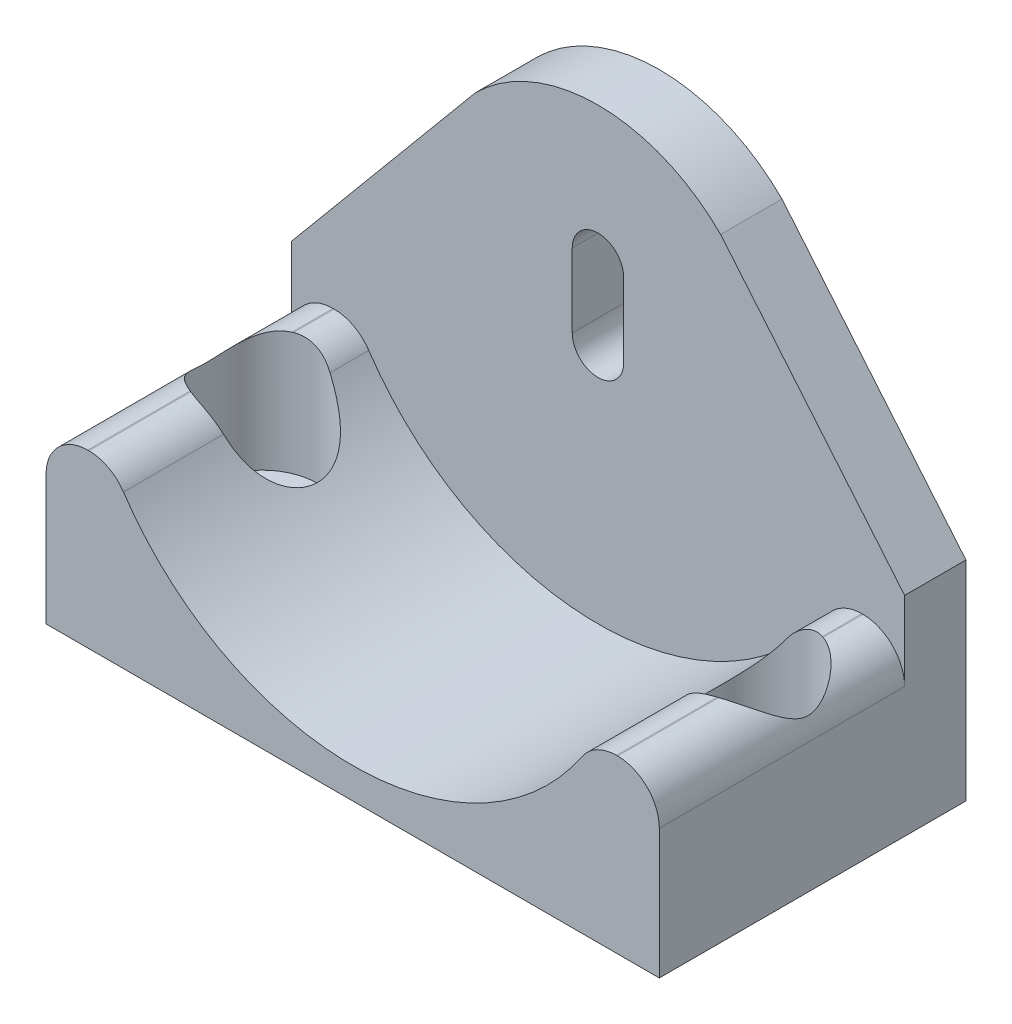
SolidWorks part; units mm, degrees
ref_plane "前视基准面" through (0, 0, 0) normal (0, 0, 1) x (1, 0, 0)
ref_plane "上视基准面" through (0, 0, 0) normal (0, 1, 0) x (1, 0, 0)
ref_plane "右视基准面" through (0, 0, 0) normal (1, 0, 0) x (0, 0, -1)
sketch "草图1" plane through (0, 0, 0) normal (0, 0, 1) x (1, 0, 0)
  line L1 (-28.2986, 3.0382) -> (21.7014, 3.0382)
  line L2 (-28.2986, 3.0382) -> (-28.2986, -13.9757)
  line L3 (-28.2986, -13.9757) -> (21.7014, -13.9757)
  line L4 (21.7014, 3.0382) -> (21.7014, -13.9757)
  line L7 (-13.2986, 21.0243) -> (-28.2986, 3.0382)
  line L8 (6.7014, 21.0243) -> (21.7014, 3.0382)
  line L12 (-3.2986, 14.0243) -> (-3.2986, 8.0243) construction
  line L13 (-1.1986, 14.0243) -> (-1.1986, 8.0243)
  line L14 (-5.3986, 14.0243) -> (-5.3986, 8.0243)
  arc A1 (-13.2986, 21.0243) -> (6.7014, 21.0243) centre (-3.2986, 11.0243) cw
  arc A2 (-1.1986, 14.0243) -> (-5.3986, 14.0243) centre (-3.2986, 14.0243) ccw
  arc A3 (-5.3986, 8.0243) -> (-1.1986, 8.0243) centre (-3.2986, 8.0243) ccw
  arc A5 (-24.3336, 3.0382) -> (17.7364, 3.0382) centre (-3.2986, 11.0243) ccw
  point P19 (-3.2986, 11.0243)
  dimension "D9" = 2.1
  dimension "D1" = 50
extrude "凸台-拉伸1" add sketch "草图1" along normal blind 25 contours A5 L1 L2 L3 L4 region at (-26.3161, 2.51, 0)
extrude "凸台-拉伸2" add sketch "草图1<5>" along normal blind 5 contours L1 A5 | A1 L7 L1 L8 A3 L14 A2 L13 region at (-20.3787, 11.6811, 0) region at (-3.2986, -2.9654, 0)
sketch "草图1<5>" plane through (0, 0, 0) normal (0, 0, 1) x (1, 0, 0) same geometry as "草图1"
sketch "草图3" plane through (0, 0, 25) normal (0, 0, 1) x (1, 0, 0)
  line L0 (-35.9406, 0) -> (33.432, 0)
  line L1 (-28.2986, 0) -> (-28.2986, 3.0382)
  line L2 (-28.2986, 3.0382) -> (-28.2986, -13.9757) construction
  line L3 (-28.2986, 3.0382) -> (-24.3336, 3.0382)
  line L4 (-28.2986, 3.0382) -> (-24.3336, 3.0382) construction
  line L5 (-24.3336, 3.0382) -> (-22.9128, 0)
  line L6 (-22.9128, 0) -> (-28.2986, 0)
  line L7 (16.3155, 0) -> (17.7364, 3.0382)
  line L8 (17.7364, 3.0382) -> (21.7014, 3.0382)
  line L9 (21.7014, 3.0382) -> (21.7014, 0)
  line L10 (21.7014, 3.0382) -> (21.7014, -13.9757) construction
  line L11 (21.7014, 0) -> (16.3155, 0)
  arc A0 (-24.3336, 3.0382) -> (17.7364, 3.0382) centre (-3.2986, 11.0243) ccw construction
  arc M1 (17.7364, 3.0382) -> (-24.3336, 3.0382) centre (-3.2986, 11.0243) cw
  line M2 (-24.3336, 3.0382) -> (-28.2986, 3.0382)
  line M3 (-28.2986, 3.0382) -> (-28.2986, -13.9757)
  line M5 (21.7014, -13.9757) -> (21.7014, 3.0382)
  line M6 (21.7014, 3.0382) -> (17.7364, 3.0382)
extrude "切除-拉伸2" cut sketch "草图3" against normal blind 20 contours L0 M3 M1 M2 | L0 M1 M5 M6 region at (-25.9658, 1.4415, 25) region at (19.3685, 1.4415, 25)
fillet "圆角3" radius 3.4 2 edges at (-22.9128, 0, 15) (-28.2986, 0, 15)
fillet "圆角4" radius 3.4 2 edges at (21.7014, 0, 15) (16.3155, 0, 15)
sketch "草图5" plane through (0, -13.9757, 0) normal (0, -1, 0) x (-1, 0, 0)
  circle A0 centre (23.1599, -12.5) radius 2.6
  circle A1 centre (-16.8401, -12.5) radius 2.6
  dimension "D3" = 5.2
  dimension "D4" = 5.2
extrude "切除-拉伸3" cut sketch "草图5" against normal blind 20
sketch "草图7" plane through (0, 0, 0) normal (0, 1, 0) x (1, 0, 0)
  circle A0 centre (-23.1599, -12.5) radius 4.5
  circle A1 centre (16.8401, -12.5) radius 4.5
  dimension "D1" = 9
  dimension "D2" = 9
extrude "切除-拉伸5" cut sketch "草图7" against normal blind 9.98
